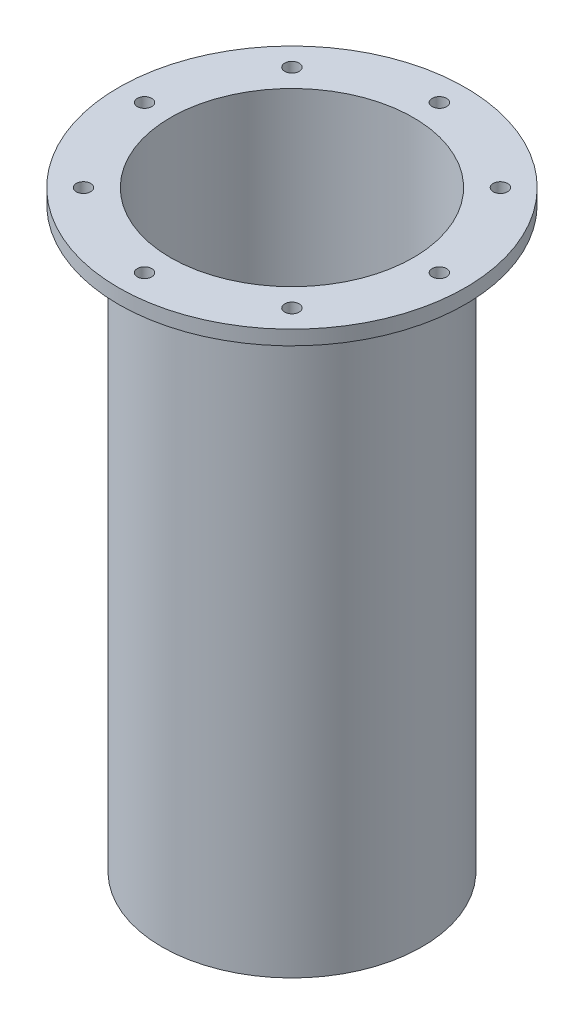
SolidWorks part; units mm, degrees
ref_plane "Front Plane" through (0, 0, 0) normal (0, 0, 1) x (1, 0, 0)
ref_plane "Top Plane" through (0, 0, 0) normal (0, 1, 0) x (1, 0, 0)
ref_plane "Right Plane" through (0, 0, 0) normal (1, 0, 0) x (0, 0, -1)
ref_axis "Axial" through (0, 55, 0) along (0, -1, 0)
sketch "Sketch1" plane through (0, 0, 0) normal (0, 1, 0) x (1, 0, 0)
  circle A0 centre (0, 0) radius 53.34
  circle A1 centre (0, 0) radius 57.15
  dimension "D1" = 114.3
  dimension "D2" = 106.68
extrude "Scheduled Chamber" add sketch "Sketch1" against normal blind 260.35
sketch "Sketch2" plane through (0, 0, 0) normal (0, 1, 0) x (1, 0, 0)
  circle A0 centre (0, 0) radius 57.15
  circle A1 centre (0, 0) radius 76.2
  dimension "D1" = 152.4
  dimension "D2" = 114.3
extrude "Flange" add sketch "Sketch2" against normal blind 6.35
sketch "Sketch3" plane through (0, 0, 0) normal (0, 1, 0) x (1, 0, 0)
  line L0 (0, -83.82) -> (0, 83.82) construction
  circle A0 centre (0, 64.77) radius 3.175
  dimension "D1" = 6.35
  dimension "D2" = 64.77
extrude "Original Bolt Hole" cut sketch "Sketch3" against normal up to next
pattern_circular "Bolt Hole Pattern" count 8 over 360 about axis through (0, 55, 0) along (0, -1, 0) of "Original Bolt Hole"
